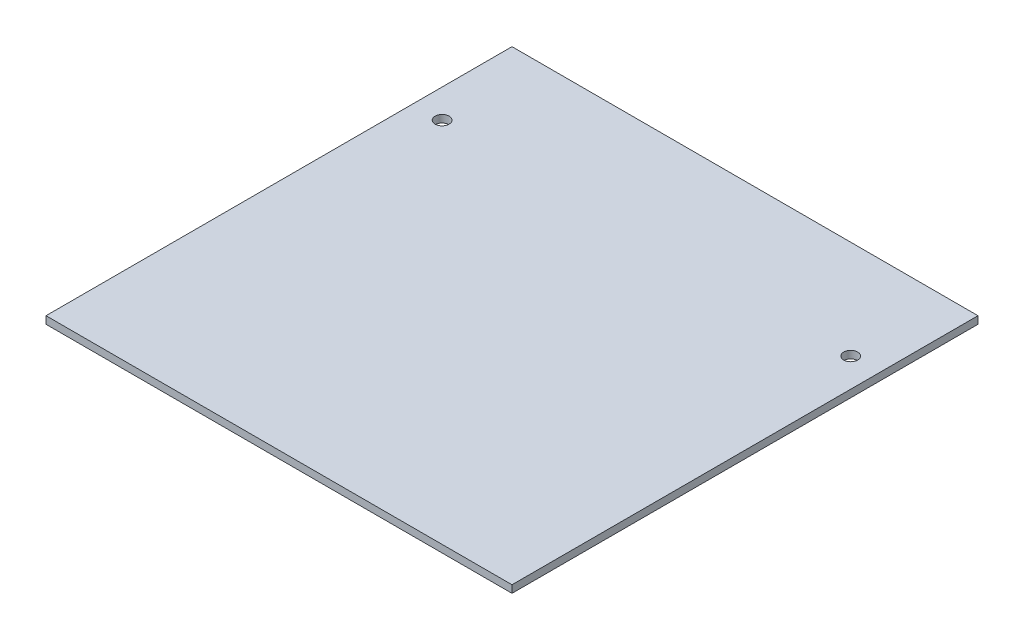
SolidWorks part; units mm, degrees
ref_plane "Front Plane" through (0, 0, 0) normal (0, 0, 1) x (1, 0, 0)
ref_plane "Top Plane" through (0, 0, 0) normal (0, 1, 0) x (1, 0, 0)
ref_plane "Right Plane" through (0, 0, 0) normal (1, 0, 0) x (0, 0, -1)
sketch "Sketch1" plane through (0, 0, 0) normal (0, 1, 0) x (1, 0, 0)
  line L1 (-50, -35) -> (-50, 65)
  line L3 (-50, 65) -> (0, 65)
  line L4 (0, -35) -> (0, 65)
  line L5 (0, -35) -> (-50, -35)
  line L6 (-59.397, 28.2843) -> (-43.8406, 43.8406) construction
  line L7 (-51.9976, -33.7676) -> (-63.9796, -15.3169) construction
  line L9 (0, 0) -> (-85, 0) construction
  line L10 (-43.8406, 43.8406) -> (0, 0) construction
  line L11 (-51.9976, -33.7676) -> (0, 0) construction
  circle A0 centre (0, 0) radius 85 construction
  circle A1 centre (-43.8406, 43.8406) radius 1.5
  circle A4 centre (-63.9796, -15.3169) radius 1.5 construction
  dimension "D7" = 3
  dimension "D17" = 170
  dimension "D2" = 100
  dimension "D5" = 35
  dimension "D6" = 50
  dimension "D8" = 62
  dimension "D9" = 22
  dimension "D10" = 22
  dimension "D14" = 45
  dimension "D15" = 33
extrude "Boss-Extrude1" add sketch "Sketch1" along normal blind 1.6
mirror "Mirror1" about plane through (0, 1.6, 35) normal (-1, 0, 0) of "Boss-Extrude1"
